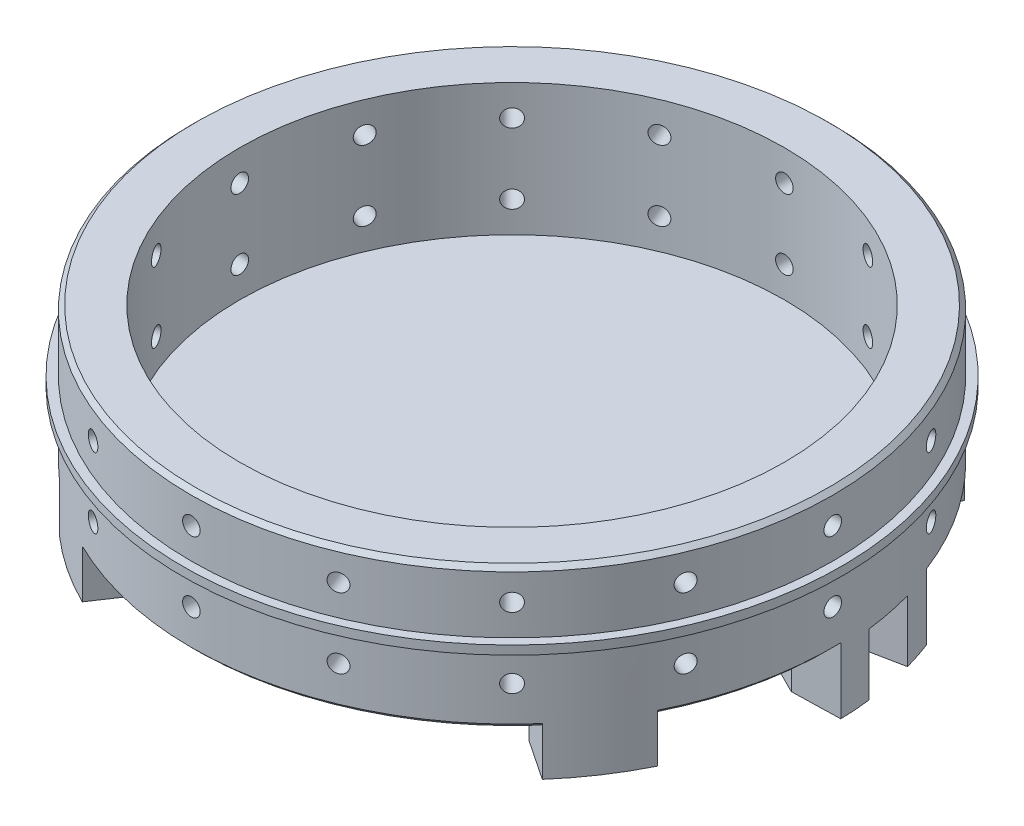
SolidWorks part; units mm, degrees
material "7075-T6, Plate (SS)"
ref_plane "Piano frontale" through (0, 0, 0) normal (0, 0, 1) x (1, 0, 0)
ref_plane "Piano superiore" through (0, 0, 0) normal (0, 1, 0) x (1, 0, 0)
ref_plane "Piano destro" through (0, 0, 0) normal (1, 0, 0) x (0, 0, -1)
sketch "Schizzo1" plane through (0, 0, 0) normal (0, 0, 1) x (1, 0, 0)
  line L1 (-73, 30) -> (-62, 30)
  line L5 (0, 0) -> (-73, 0) construction
  line L7 (-73, 14) -> (-73, 0)
  line L10 (0, 0) -> (0, 16) construction
  line L13 (-73, 14) -> (-75, 14)
  line L14 (-75, 14) -> (-75, 16)
  line L15 (-75, 16) -> (-73, 16)
  line L16 (-73, 16) -> (-73, 30)
  line L19 (-62, 16) -> (-62, 14) construction
  line L21 (-73, 14) -> (0, 14) construction
  line L22 (-73, 16) -> (0, 16) construction
  line L23 (0, 16) -> (0, 14) construction
  line L24 (-73, 0) -> (-62, 0)
  line L25 (-62, 30) -> (-62, 16)
  line L26 (-62, 0) -> (-62, 14)
  line L27 (-62, 16) -> (0, 16)
  line L28 (-62, 14) -> (0, 14)
  line L29 (0, 14) -> (0, 16)
  dimension "D1" = 146
  dimension "D2" = 2
  dimension "D3" = 150
  dimension "D4" = 11
  dimension "D5" = 62
  dimension "D6" = 14
  dimension "D7" = 14
revolve "Rivoluzione1" add sketch "Schizzo1" angle 360 about L10 region at (-57.6747, 15, 0)
hole_wizard "Ø4.0 (4) Diameter Hole1" positions "Schizzo3D1" profile "Schizzo5" hole size "Ø4.0" standard "ISO"
sketch3d "Schizzo3D1"
  line L0 (-73, 16, 0) -> (-73, 30, 0) construction
  circle A0 centre (0, 30, 0) radius 73 construction
  circle A1 centre (0, 30, 0) radius 73 construction
  circle A2 centre (0, 16, 0) radius 73 construction
  circle A3 centre (0, 16, 0) radius 73 construction
  point P0 (-73, 23, 0)
  point P4 (0, -43, 0)
  point P6 (0, -43, 0)
  point P9 (0, -57, 0)
  point P11 (0, -57, 0)
  point P17 (-73, 23, 0)
sketch "Schizzo5" plane through (-73, 23, 0) normal (0, 1, 0) x (0, 0, 1)
  line L0 (0, 0) -> (0, 19)
  line L1 (0, 19) -> (2, 17.7983)
  line L2 (2, 17.7983) -> (2, 0)
  line L5 (2, 0) -> (0, 0)
  line L10 (0, 19) -> (-2, 17.7983) construction
  line L11 (0, -6.35) -> (0, 107.95) construction
  dimension "Hole Dia." = 4
  dimension "Hole Depth" = 19
  dimension "Drill Angle" = 118
hole_wizard "Foro Ø4.0 (4)-3" positions "Schizzo3D3" profile "Schizzo9" hole size "Ø4.0" standard "ISO"
sketch3d "Schizzo3D3"
  line L0 (73, 0, 0) -> (73, 14, 0) construction
  circle A1 centre (0, 14, 0) radius 73 construction
  circle A3 centre (0, 14, 0) radius 73 construction
  circle A4 centre (0, 0, 0) radius 73 construction
  point P0 (73, 7, 0)
  point P2 (73, 7, 0)
  point P9 (0, -59, 0)
  point P13 (0, -59, 0)
  point P18 (73, 7, 0)
  point P22 (0, -73, 0)
sketch "Schizzo9" plane through (73, 7, 0) normal (0, 1, 0) x (0, 0, -1)
  line L0 (0, 0) -> (0, 19)
  line L1 (0, 19) -> (2, 17.7983)
  line L2 (2, 17.7983) -> (2, 0)
  line L5 (2, 0) -> (0, 0)
  line L10 (0, 19) -> (-2, 17.7983) construction
  line L11 (0, -6.35) -> (0, 107.95) construction
  dimension "Hole Dia." = 4
  dimension "Hole Depth" = 19
  dimension "Drill Angle" = 118
pattern_circular "RipetizioneCircolare7" count 16 over 360 about axis through (0, 14, 0) along (0, -1, 0) of "Foro Ø4.0 (4)-3"
pattern_circular "CirPattern1" count 16 over 360 about axis through (0, 16, 0) along (0, -1, 0) of "Ø4.0 (4) Diameter Hole1"
sketch "Sketch7" plane through (0, 14, 0) normal (0, -1, 0) x (1, 0, 0)
  circle A0 centre (0, 0) radius 62 construction
  circle A1 centre (0, 0) radius 62
extrude "Cut-Extrude4" cut sketch "Sketch7" against normal through all
sketch "Sketch8" plane through (0, 0, 0) normal (0, -1, 0) x (1, 0, 0)
  circle A0 centre (0, 0) radius 73 construction
  circle A1 centre (0, 0) radius 73
extrude "Boss-Extrude20" add sketch "Sketch8" along normal blind 2
sketch "Sketch6" plane through (0, -2, 0) normal (0, -1, 0) x (1, 0, 0)
  line L0 (-61.6535, 6.546) -> (-59.4654, 17.546) construction
  line L1 (-61.6535, 6.546) -> (-72.4798, 8.6995)
  line L2 (-72.4798, 8.6995) -> (-70.2917, 19.6995) construction
  line L3 (-70.2917, 19.6995) -> (-59.4654, 17.546)
  line L4 (0, 0) -> (-68.1234, 26.2337) construction
  line L5 (0, 0) -> (-72.977, 1.8329) construction
  line L6 (-72.977, 1.8329) -> (-61.6535, 6.546) construction
  line L7 (-59.4654, 17.546) -> (-68.1234, 26.2337) construction
  line L8 (-61.9805, 1.5567) -> (-53.6957, 5.7011)
  line L9 (-51.79, 15.2813) -> (-57.8582, 22.2807)
  line L11 (0, 0) -> (-71.5973, 14.2416) construction
  line L12 (-61.9805, 1.5567) -> (-61.6535, 6.546) construction
  line L13 (-61.6535, 6.546) -> (0, 0) construction
  line L14 (0, 0) -> (-59.4654, 17.546) construction
  line L15 (-72.4798, 8.6995) -> (-71.5973, 14.2416) construction
  line L16 (-71.5973, 14.2416) -> (-70.2917, 19.6995) construction
  line L17 (-72.977, 1.8329) -> (-61.9805, 1.5567)
  line L18 (-68.1234, 26.2337) -> (-57.8582, 22.2807)
  line L19 (-73, 0) -> (-71.5973, 14.2416) construction
  line L20 (-71.5973, 14.2416) -> (-67.4432, 27.9359) construction
  arc A0 (-72.9726, 2) -> (-72.9726, -2) centre (0, 0) ccw construction
  arc A1 (-72.9726, 2) -> (-72.9726, -2) centre (0, 0) ccw
  arc A5 (-57.8582, 22.2807) -> (-59.4654, 17.546) centre (0, 0) ccw construction
  arc A6 (-66.6525, 29.7732) -> (-68.1833, 26.0776) centre (0, 0) ccw construction
  arc A7 (-53.9805, 1.3558) -> (-50.3903, 19.4048) centre (0, 0) cw
  circle A8 centre (0, 0) radius 73 construction
  arc A9 (-68.1234, 26.2337) -> (-72.977, 1.8329) centre (0, 0) ccw
  arc A10 (-61.9805, 1.5567) -> (-57.8582, 22.2807) centre (0, 0) cw construction
  circle A11 centre (0, 0) radius 62 construction
  circle A12 centre (0, 0) radius 62 construction
  arc A13 (-66.6525, 29.7732) -> (-68.1833, 26.0776) centre (0, 0) ccw
  point P0 (-59.4654, 17.546)
  point P1 (-61.6535, 6.546)
  point P12 (-53.9805, 1.3558)
  dimension "D1" = 5
  dimension "D2" = 8
  dimension "D3" = 11
extrude "Boss-Extrude19" add sketch "Sketch6" along normal blind 14 contours L3 L1 L0 | L1 | L8 | L0 | L9 | L3 region at (-63.119, -2, 12.5552)
sketch "Sketch3" plane through (0, -16, 0) normal (0, -1, 0) x (1, 0, 0)
  line L3 (-72.592, 7.7074) -> (0, 0) construction
  line L4 (0, 0) -> (-70.0157, 20.659) construction
  line L5 (-61.5559, 7.0364) -> (-59.563, 17.0556)
  line L8 (-62.1439, 6.6436) -> (-72.4798, 8.6995)
  line L9 (-72.4798, 8.6995) -> (-70.2917, 19.6995) construction
  line L10 (-70.2917, 19.6995) -> (-59.9558, 17.6436)
  line L11 (-61.5559, 7.0364) -> (-62.1439, 6.6436)
  line L12 (-59.9558, 17.6436) -> (-59.563, 17.0556)
  arc A3 (-68.1234, 26.2337) -> (-72.977, 1.8329) centre (0, 0) ccw construction
  arc A4 (-61.9805, 1.5567) -> (-57.8582, 22.2807) centre (0, 0) cw construction
  arc A8 (-70.2917, 19.6995) -> (-72.4798, 8.6995) centre (0, 0) ccw
  point P11 (-61.6535, 6.546)
  point P13 (-59.4654, 17.546)
extrude "Cut-Extrude3" cut sketch "Sketch3" against normal blind 14
hole_wizard "Ø4.0 (4) Diameter Hole3" positions "3DSketch2" profile "Sketch4" hole size "Ø4.0" standard "ISO"
sketch3d "3DSketch2"
  line L7 (-61.5559, -2, 7.0364) -> (-59.563, -2, 17.0556) construction
  line L8 (-61.5559, -16, 7.0364) -> (-59.563, -16, 17.0556) construction
  line L9 (-61.5559, -2, 7.0364) -> (-59.563, -2, 17.0556)
  line L10 (-61.5559, -16, 7.0364) -> (-59.563, -16, 17.0556)
  line L11 (-60.5594, -16, 12.046) -> (-60.5594, -2, 12.046)
  point P46 (-60.5594, -9, 12.046)
  point P49 (-60.5594, -9, 12.046)
sketch "Sketch4" plane through (-60.5594, -9, 12.046) normal (0, 1, 0) x (0.1951, 0, 0.9808)
  line L0 (0, 0) -> (0, 19)
  line L1 (0, 19) -> (2, 17.7983)
  line L2 (2, 17.7983) -> (2, 0)
  line L5 (2, 0) -> (0, 0)
  line L10 (0, 19) -> (-2, 17.7983) construction
  line L11 (0, -6.35) -> (0, 107.95) construction
  dimension "Hole Dia." = 4
  dimension "Hole Depth" = 19
  dimension "Drill Angle" = 118
pattern_circular "CirPattern2" count 2 over 360 about axis through (0, -2, 0) along (0, -1, 0) of "Boss-Extrude19", "Cut-Extrude3", "Ø4.0 (4) Diameter Hole3"
sketch "Sketch9" plane through (0, -2, 0) normal (0, -1, 0) x (1, 0, 0)
  line L0 (-39.2847, 58.7938) -> (-26.2017, 56.1914)
  line L1 (58.7938, 39.2847) -> (-39.2847, 58.7938) construction
  line L2 (58.7938, 39.2847) -> (39.2847, -58.7938) construction
  line L3 (39.2847, -58.7938) -> (-58.7938, -39.2847) construction
  line L4 (-39.2847, 58.7938) -> (-58.7938, -39.2847) construction
  line L5 (58.7938, 39.2847) -> (-58.7938, -39.2847) construction
  line L6 (39.2847, -58.7938) -> (-39.2847, 58.7938) construction
  line L7 (-39.2847, 58.7938) -> (-41.8871, 45.7107)
  line L8 (-26.2017, 56.1914) -> (-32.3739, 65.4288)
  line L9 (-41.8871, 45.7107) -> (-48.0594, 54.9481)
  line L10 (-67.4432, 27.9359) -> (0, 0) construction
  line L11 (0, 0) -> (-73, 0) construction
  line L12 (-67.4432, 27.9359) -> (-73, 0) construction
  line L13 (-70.2216, 13.9679) -> (0, 0) construction
  circle A2 centre (0, 0) radius 62 construction
  circle A3 centre (0, 0) radius 62 construction
  arc A4 (-72.977, 1.8329) -> (68.1234, -26.2337) centre (0, 0) ccw construction
  arc A5 (-32.3739, 65.4288) -> (-48.0594, 54.9481) centre (0, 0) ccw
  arc A6 (-72.9726, 2) -> (-72.9726, -2) centre (0, 0) ccw construction
  arc A7 (-66.6525, 29.7732) -> (-68.1833, 26.0776) centre (0, 0) ccw construction
  arc A8 (-72.9726, 2) -> (-72.9726, -2) centre (0, 0) ccw
  arc A9 (-66.6525, 29.7732) -> (-68.1833, 26.0776) centre (0, 0) ccw
  point P0 (0, 0)
  arc M15 (-72.977, 1.8329) -> (68.1234, -26.2337) centre (0, 0) ccw
  dimension "D1" = 100
  dimension "D2" = 100
extrude "Boss-Extrude21" add sketch "Sketch9" along normal blind 10 contours L9 L7 L0 L8 M15 region at (-40.8747, -2, 52.3097)
pattern_circular "CirPattern3" count 4 over 360 about axis through (0, -2, 0) along (0, -1, 0) of "Boss-Extrude21"
chamfer "Smusso3" distance 1 angle 45 1 edges at (0, 30, -73)
chamfer "Chamfer1" distance 1 angle 45 6 edges at (71.2851, -2, 15.73) (-14.2416, -2, -71.5973) (59.8393, -2, -41.8122) (-71.2851, -2, -15.73) (-59.8393, -2, 41.8122) (14.2416, -2, 71.5973)
